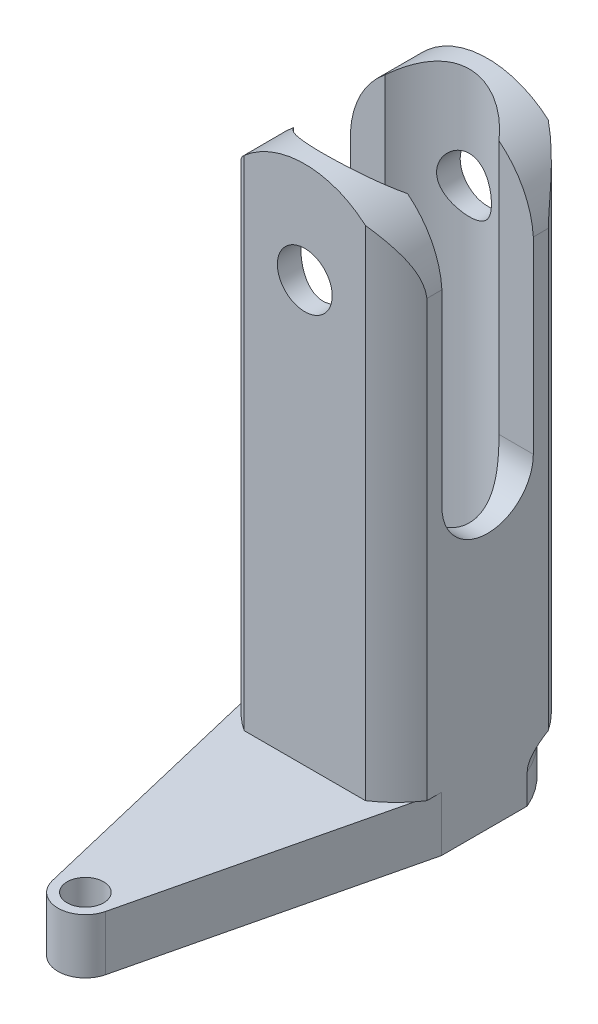
SolidWorks part; units mm, degrees
material "6061 Alloy"
ref_plane "Front Plane" through (0, 0, 0) normal (0, 0, 1) x (1, 0, 0)
ref_plane "Top Plane" through (0, 0, 0) normal (0, 1, 0) x (1, 0, 0)
ref_plane "Right Plane" through (0, 0, 0) normal (1, 0, 0) x (0, 0, -1)
sketch "Sketch1" plane through (0, 0, 0) normal (0, 1, 0) x (1, 0, 0)
  circle A0 centre (0, 0) radius 2
  circle A1 centre (0, 0) radius 6
  dimension "D1" = 4
extrude "Boss-Extrude1" add sketch "Sketch1" along normal blind 28.5
ref_plane "Plane1" through (0, -3, 0) normal (0, -1, 0) x (-1, 0, 0)
sketch "Sketch2" plane through (0, -3, 0) normal (0, -1, 0) x (-1, 0, 0)
  line L0 (-1.459, -17.3485) -> (-5.3005, -1.2661)
  line L5 (0, 13.1723) -> (0, -13.1723) construction
  line L6 (1.459, -17.3485) -> (5.3005, -1.2661)
  circle A0 centre (0, 0) radius 2
  arc A1 (5.3005, -1.2661) -> (-5.3005, -1.2661) centre (0, 0) ccw
  circle A2 centre (0, 0) radius 6 construction
  circle A3 centre (0, -17) radius 1
  arc A4 (-1.459, -17.3485) -> (1.459, -17.3485) centre (0, -17) ccw
  point P4 (0, -6)
  dimension "D1" = 17
extrude "Boss-Extrude2" add sketch "Sketch2" against normal up to surface (3 mm away) up to face at (0, 0, 6)
sketch "Sketch3" plane through (0, 28.5, 0) normal (0, 1, 0) x (1, 0, 0)
  line L1 (-3.1218, -2.5) -> (-3.1225, -2.5)
  line L3 (-3.1218, 2.5) -> (-3.1225, 2.5)
  line L8 (3.1225, 2.5) -> (3.1293, 2.5)
  line L9 (3.1225, -2.5) -> (3.1293, -2.5)
  circle A5 centre (0, 0) radius 4
  point P0 (0, 0)
  dimension "D1" = 5
extrude "Cut-Extrude1" cut sketch "Sketch3" against normal blind 23 contours A5 region at (3.6675, 28.5, 1.2873)
sketch "Sketch4" plane through (0, 0, 0) normal (0, 1, 0) x (1, 0, 0)
  line L0 (-6.5, 6.5) -> (6.5, 6.5)
  line L1 (-5, -5) -> (5, -5)
  line L2 (-5, -5) -> (-5, 5)
  line L3 (-5, 5) -> (5, 5)
  line L4 (5, -5) -> (5, 5)
  line L5 (-5, -5) -> (5, 5) construction
  line L6 (-5, 5) -> (5, -5) construction
  line L7 (6.5, -6.5) -> (6.5, 6.5)
  line L8 (-6.5, -6.5) -> (6.5, -6.5)
  line L9 (-6.5, -6.5) -> (-6.5, 6.5)
  line L10 (-3.5, 3.5) -> (3.5, 3.5)
  line L11 (3.5, -3.5) -> (3.5, 3.5)
  line L12 (-3.5, -3.5) -> (3.5, -3.5)
  line L13 (-3.5, -3.5) -> (-3.5, 3.5)
  point P0 (0, 0)
  arc M4 (4.7172, -3.7078) -> (-4.7172, -3.7078) centre (0, 0) cw
  line M5 (-4.7172, -3.7078) -> (-1.459, -17.3485)
  line M7 (1.459, -17.3485) -> (4.7172, -3.7078)
  dimension "D1" = 10
  dimension "D2" = 10
  dimension "D3" = 1.5
  dimension "D4" = 1.5
extrude "Cut-Extrude2" cut sketch "Sketch4" along normal through all contours L9 L8 L7 L0 L4 L1 L2 L3 M5 M4 M7 | L8 L1 M5 M7 M4 | L1 M4 region at (0, 0, -6.3162) region at (-4.1424, 0, 5.7292) region at (0, 0, 5.403)
sketch "Sketch8" plane through (0, 0, 5) normal (0, 0, 1) x (1, 0, 0)
  line L0 (-5, 0) -> (-5, 28.5) construction
  line L1 (5, 0) -> (5, 28.5) construction
  line L2 (-5, 23.7912) -> (-6.4415, 23.7912)
  line L3 (-6.4415, 23.7912) -> (-6.4415, 29.3856)
  line L4 (-6.4415, 29.3856) -> (5.9884, 29.3856)
  line L5 (5, 23.7912) -> (5.9884, 23.7912)
  line L6 (5.9884, 23.7912) -> (5.9884, 29.3856)
  arc A0 (-5, 23.7912) -> (5, 23.7912) centre (0, 23.491) cw
extrude "Cut-Extrude5" cut sketch "Sketch8" against normal through all contours L3 L4 L6 L5 A0 L2
sketch "Sketch9" plane through (-5, 0, 0) normal (-1, 0, 0) x (0, 0, 1)
  line L1 (-2.5, 28.5) -> (2.5, 28.5)
  line L5 (-2.5, 28.5) -> (2.5, 28.5)
  line L6 (-2.5, 28.5) -> (-2.5, 13.5)
  line L8 (2.5, 28.5) -> (2.5, 13.5)
  line L9 (-5, 0) -> (-5, 27.2447) construction
  line L11 (-3.9999, 28.5) -> (-5, 28.5) construction
  arc A0 (-2.5, 13.5) -> (2.5, 13.5) centre (0, 13.5) ccw
  point P3 (0, 0)
  point P11 (0, 0)
  line M3 (3.3166, 23.7912) -> (-3.3166, 23.7912)
  dimension "D1" = 5
  dimension "D2" = 2.5
  dimension "D3" = 15
extrude "Cut-Extrude6" cut sketch "Sketch9" against normal through all contours L8 L1 L6 M3 | L6 A0 L8 M3 region at (-5, 26.1456, 0) region at (-5, 17.6511, 0)
sketch "Sketch10" plane through (0, 0, 0) normal (0, 1, 0) x (1, 0, 0)
  line L0 (-5, 3.3166) -> (-5, -3.3166)
  line L1 (-5, -3.3166) -> (-6.3874, -3.3166)
  line L2 (-6.3874, -3.3166) -> (-6.3874, 5)
  line L3 (-5, 5) -> (5, 5)
  line L4 (5, 5) -> (5, -3.3166)
  line L5 (5, -3.3166) -> (6.9833, -3.3166)
  line L6 (6.9833, -3.3166) -> (6.9833, 6.8209)
  line L7 (6.9833, 6.8209) -> (-6.3874, 6.8209)
  line L8 (-6.3874, 6.8209) -> (-6.3874, 5)
  line L9 (-5, 3.3166) -> (-5, 5)
extrude "Cut-Extrude7" cut sketch "Sketch10" against normal through all contours L7 L8 L2 L1 L0 L9 L3 L4 L5 L6
sketch "Sketch11" plane through (0, 0, 5) normal (0, 0, 1) x (1, 0, 0)
  line L0 (5, -3) -> (1.459, -3) construction
  circle A0 centre (0, 23) radius 1.5
  dimension "D1" = 26
extrude "Cut-Extrude8" cut sketch "Sketch11" against normal through all
fillet "Fillet1" radius 2 2 edges at (3.8534, 0, -3.8534) (-3.8534, 0, -3.8534)
